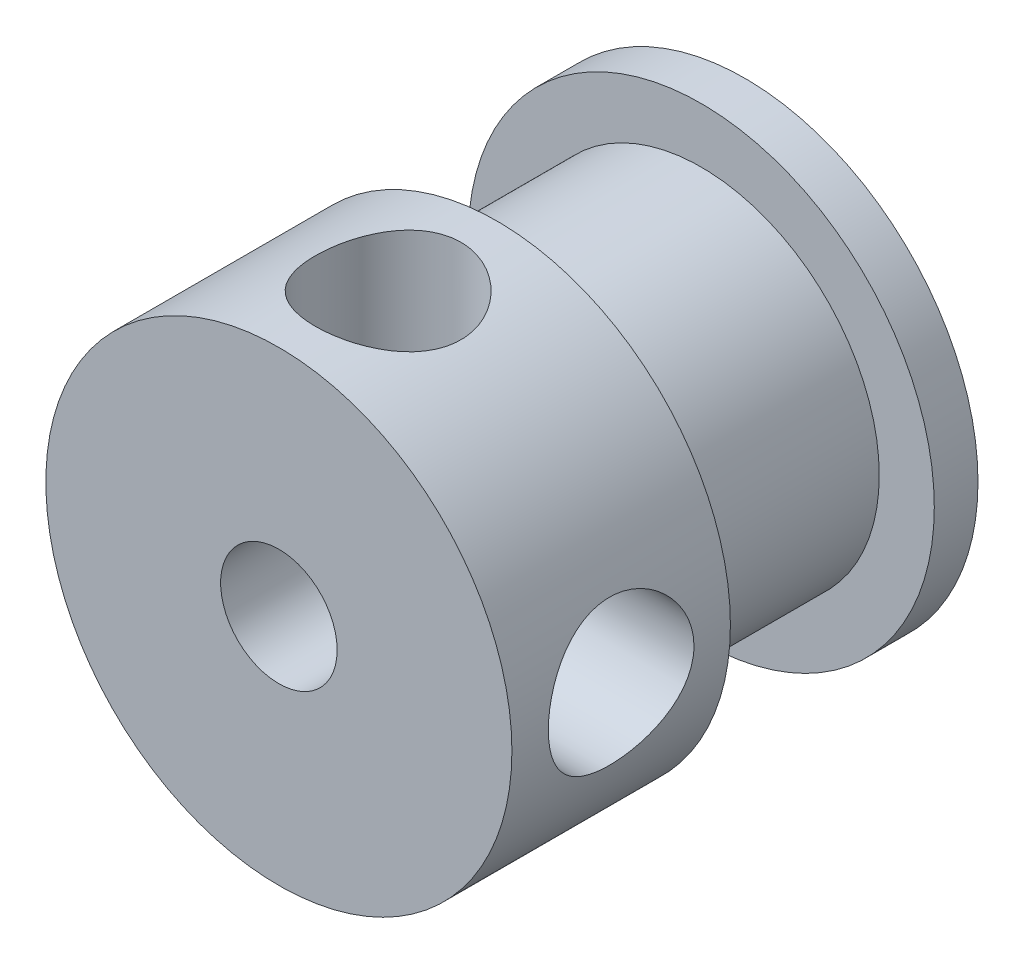
SolidWorks part; units mm, degrees
ref_plane "Front Plane" through (0, 0, 0) normal (0, 0, 1) x (1, 0, 0)
ref_plane "Top Plane" through (0, 0, 0) normal (0, 1, 0) x (1, 0, 0)
ref_plane "Right Plane" through (0, 0, 0) normal (1, 0, 0) x (0, 0, -1)
sketch "Sketch1" plane through (0, 0, 0) normal (0, 0, 1) x (1, 0, 0)
  circle A0 centre (0, 0) radius 8
extrude "Boss-Extrude1" add sketch "Sketch1" along normal blind 1.5
sketch "Sketch2" plane through (0, 0, 1.5) normal (0, 0, 1) x (1, 0, 0)
  circle A0 centre (0, 0) radius 6.11
extrude "Boss-Extrude2" add sketch "Sketch2" along normal blind 7
sketch "Sketch4" plane through (0, 0, 8.5) normal (0, 0, 1) x (1, 0, 0)
  circle A0 centre (0, 0) radius 8
extrude "Boss-Extrude4" add sketch "Sketch4" along normal blind 7.5
sketch "Sketch6" plane through (0, 0, 16) normal (0, 0, 1) x (1, 0, 0)
  circle A0 centre (0, 0) radius 2
extrude "Cut-Extrude1" cut sketch "Sketch6" against normal up to surface (16 mm away) up to face at (8, 0, 0)
ref_axis "Axis1" through (0, 0, 0) along (0, 0, 1)
ref_plane "Plane1" through (0, 0, 0) normal (-1, 0, 0) x (0, 0, 1)
sketch "Sketch7" plane through (0, 0, 0) normal (-1, 0, 0) x (0, 0, 1)
  line L0 (16, 0) -> (12.25, 0) construction
  line L1 (16, -8) -> (16, 8) construction
  line L2 (0, 0) -> (16, 0) construction
  circle A0 centre (12.25, 0) radius 2.5
extrude "Cut-Extrude2" cut sketch "Sketch7" against normal up to surface (8 mm away) up to face at (8, 0, 16)
ref_plane "Plane2" through (0, 0, 0) normal (0, -1, 0) x (0, 0, 1)
sketch "Sketch8" plane through (0, 0, 0) normal (0, -1, 0) x (0, 0, 1)
  line L0 (16, 0) -> (12.25, 0) construction
  line L1 (16, -8) -> (16, 8) construction
  line L2 (11, 0) -> (-11, 0) construction
  circle A0 centre (12.25, 0) radius 2.5
extrude "Cut-Extrude3" cut sketch "Sketch8" against normal up to surface (8 mm away) up to face at (7.9878, 0.4424, 9.7894)
